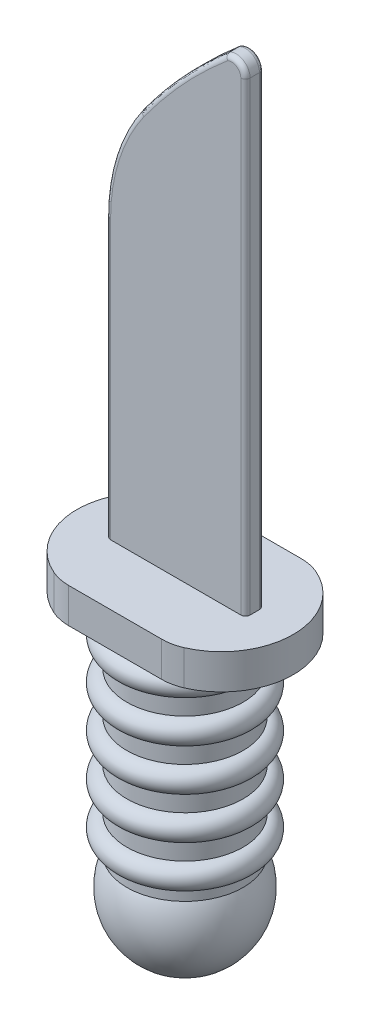
SolidWorks part; units mm, degrees
ref_plane "Front Plane" through (0, 0, 0) normal (0, 0, 1) x (1, 0, 0)
ref_plane "Top Plane" through (0, 0, 0) normal (0, 1, 0) x (1, 0, 0)
ref_plane "Right Plane" through (0, 0, 0) normal (1, 0, 0) x (0, 0, -1)
sketch "Sketch1" plane through (0, 0, 0) normal (0, 1, 0) x (1, 0, 0)
  circle A0 centre (0, 0) radius 1.25
  dimension "D1" = 2.5
extrude "Boss-Extrude1" add sketch "Sketch1" along normal blind 4.5
sketch "Sketch2" plane through (0, 4.5, 0) normal (0, 1, 0) x (1, 0, 0)
  line L2 (1, 1.5) -> (-1, 1.5)
  line L3 (-2.5524, 0) -> (2.5524, 0) construction
  line L4 (1, -1.5) -> (0.0127, -1.5)
  line L6 (0, 1.379) -> (0, -1.3646)
  line L7 (-1, -1.5) -> (0.0127, -1.5)
  arc A2 (1.4, -1.4165) -> (1.4, 1.4165) centre (0.7818, 0) ccw
  arc A3 (1.4, 1.4165) -> (1, 1.5) centre (1, 0.5) ccw
  arc A4 (1, -1.5) -> (1.4, -1.4165) centre (1, -0.5) ccw
  arc A5 (-1, -1.5) -> (-1.4, -1.4165) centre (-1, -0.5) cw
  arc A6 (-1.4, -1.4165) -> (-1.4, 1.4165) centre (-0.7818, 0) cw
  arc A7 (-1.4, 1.4165) -> (-1, 1.5) centre (-1, 0.5) cw
  point P26 (0, 1.25)
  circle M1 centre (0, 0) radius 1.25
  dimension "D1" = 1
  dimension "D2" = 1
  dimension "D3" = 1.5
  dimension "D4" = 1.5
  dimension "D5" = 1
  dimension "D6" = 1
  dimension "D7" = 1.4
extrude "Boss-Extrude2" add sketch "Sketch2" along normal blind 0.75 contours A7 A6 A5 L7 L2 M1 | L4 A4 A2 A3 L2 M1 | L6 M1 | L6 M1 region at (1.193, 4.5, -1.4247) region at (0.5305, 4.5, 0) region at (-0.5305, 4.5, 0)
dome "Dome1" faces to dome 1 distance 2 reverse direction no elliptical dome no face at (0, 0, 1.25) parameters "D1"=2
sketch "Sketch3" plane through (0, 0, 0) normal (0, 0, 1) x (1, 0, 0)
  line L0 (1.5, 5.25) -> (1.5, 15.25)
  line L2 (1.5, 5.25) -> (-1.5, 5.25)
  line L4 (-1.5, 5.25) -> (-1.5, 11.232)
  line L6 (0, -1.65) -> (0, 1.65) construction
  line L7 (-1, 5.25) -> (-1.4, 5.25) construction
  line L8 (1.4, 5.25) -> (1, 5.25) construction
  arc A0 (1.5, 15.25) -> (1.0647, 15.5178) centre (1.2, 15.25) ccw
  arc A1 (-0.7648, 13.5431) -> (-1.5, 11.232) centre (2.5, 11.232) ccw
  spline S0 degree 2 poles (-0.7648, 13.5431) (0.0315, 14.6437) (1.0647, 15.5178) knots 0 0 0 1 1 1
  dimension "D3" = 0.3
  dimension "D4" = 4
  dimension "D1" = 1.5
  dimension "D2" = 1.5
  dimension "D5" = 10
extrude "Boss-Extrude3" add sketch "Sketch3" along normal blind 0.2 and the other way blind 0.2
fillet "Fillet3" radius 0.1 10 edges at (1.3572, 15.5055, -0.2) (-1.3118, 12.4446, -0.2) (-1.5, 8.241, 0.2) (1.3572, 15.5055, 0.2) (1.5, 10.25, -0.2) (-1.5, 8.241, -0.2) (-1.3118, 12.4446, 0.2) (1.5, 10.25, 0.2)
ref_plane "Plane1" through (0, 0.5, 0) normal (0, 1, 0) x (1, 0, 0)
sketch "Sketch4" plane through (0, 0.5, 0) normal (0, 1, 0) x (1, 0, 0)
  circle A0 centre (0, 0) radius 1.25
sketch "Sketch5" plane through (0, 0, 0) normal (0, 0, 1) x (1, 0, 0)
  line L0 (1.25, 0.5) -> (-1.25, 0.5) construction
  line L1 (1.65, 0.5) -> (-1.65, 0.5) construction
  circle A0 centre (-1.25, 0.5) radius 0.25
sweep "Sweep1" add profiles "Sketch5" path "Sketch4"
ref_axis "Axis1" through (0, -2.2875, 0) along (0, 1, 0)
pattern_linear "LPattern1" count 5 spacing 0.9 along (0, 1, 0) of "Sweep1"
